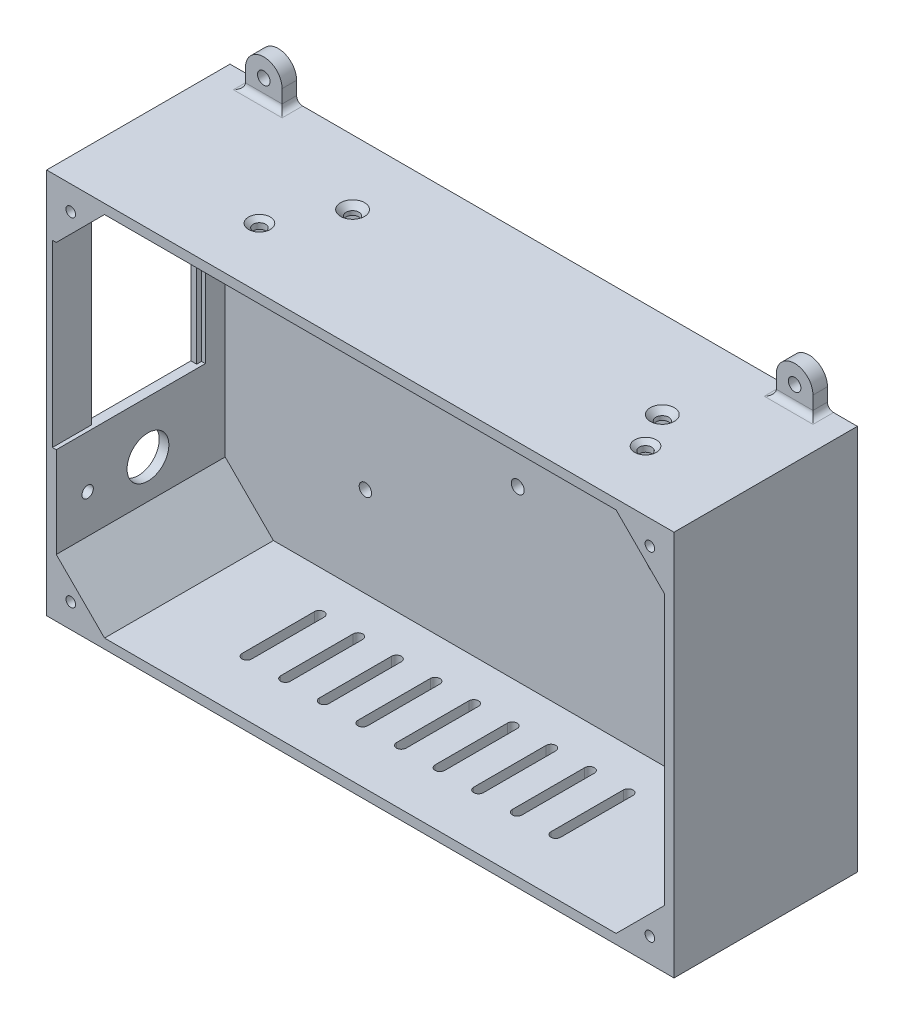
SolidWorks part; units mm, degrees
material "PET"
ref_plane "Front Plane" through (0, 0, 0) normal (0, 0, 1) x (1, 0, 0)
ref_plane "Top Plane" through (0, 0, 0) normal (0, 1, 0) x (1, 0, 0)
ref_plane "Right Plane" through (0, 0, 0) normal (1, 0, 0) x (0, 0, -1)
sketch "Sketch1" plane through (0, 0, 0) normal (0, 0, 1) x (1, 0, 0)
  line L1 (0, 0) -> (165.1, 0)
  line L2 (0, 0) -> (0, 101.6)
  line L3 (0, 101.6) -> (165.1, 101.6)
  line L4 (165.1, 0) -> (165.1, 101.6)
  dimension "D1" = 101.6
  dimension "D2" = 165.1
extrude "Boss-Extrude1" add sketch "Sketch1" along normal blind 3.81
sketch "Sketch2" plane through (0, 0, 3.81) normal (0, 0, 1) x (1, 0, 0)
  line L0 (165.1, 101.6) -> (0, 101.6)
  line L1 (0, 101.6) -> (0, 0)
  line L2 (0, 0) -> (165.1, 0)
  line L3 (165.1, 0) -> (165.1, 101.6)
  line L4 (2.54, 99.06) -> (162.56, 99.06)
  line L5 (162.56, 99.06) -> (162.56, 2.54)
  line L6 (162.56, 2.54) -> (2.54, 2.54)
  line L7 (2.54, 2.54) -> (2.54, 99.06)
  dimension "D1" = 2.54
  dimension "D2" = 2.54
  dimension "D3" = 2.54
  dimension "D4" = 2.54
extrude "Boss-Extrude2" add sketch "Sketch2" along normal blind 44.45
sketch "Sketch3" plane through (0, 0, 3.81) normal (0, 0, 1) x (1, 0, 0)
  line L0 (165.1, 0) -> (165.1, 101.6) construction
  line L1 (165.1, 101.6) -> (0, 101.6) construction
  line L2 (149.86, 99.06) -> (162.56, 86.36)
  line L3 (162.56, 99.06) -> (2.54, 99.06) construction
  line L4 (162.56, 2.54) -> (162.56, 99.06) construction
  line L5 (162.56, 86.36) -> (162.56, 99.06)
  line L6 (162.56, 99.06) -> (149.86, 99.06)
  circle A0 centre (158.75, 95.25) radius 3.81 construction
  circle A1 centre (158.75, 95.25) radius 1.27
  dimension "D1" = 7.62
  dimension "D4" = 2.54
  dimension "D2" = 6.35
  dimension "D3" = 6.35
  dimension "D5" = 12.7
extrude "Boss-Extrude3" add sketch "Sketch3" along normal up to surface (44.45 mm away) contours L2 L5 L6 up to face at (82.55, 50.8, 48.26)
extrude "Cut-Extrude1" cut sketch "Sketch3<3>" against normal blind 15.875 from surface contours A1 starting at face at (82.55, 50.8, 48.26)
sketch "Sketch3<3>" plane through (0, 0, 3.81) normal (0, 0, 1) x (1, 0, 0) same geometry as "Sketch3"
ref_plane "Plane1" through (82.55, 0, 0) normal (1, 0, 0) x (0, 0, -1)
mirror "Mirror1" about plane through (82.55, 0, 0) normal (1, 0, 0) of "Cut-Extrude1", "Boss-Extrude3"
ref_plane "Plane2" through (0, 50.8, 0) normal (0, -1, 0) x (-1, 0, 0)
mirror "Mirror2" about plane through (0, 50.8, 0) normal (0, -1, 0) of "Mirror1"
sketch "Sketch6" plane through (0, 0, 0) normal (-1, 0, 0) x (0, 0, 1)
  line L0 (24.13, 0) -> (24.13, 25.4) construction
  line L1 (48.26, 0) -> (0, 0) construction
  line L2 (24.13, 86.36) -> (24.13, 101.6) construction
  line L3 (10.287, 86.36) -> (37.973, 86.36)
  line L4 (10.287, 86.36) -> (10.287, 39.116)
  line L5 (10.287, 39.116) -> (37.973, 39.116)
  line L6 (37.973, 86.36) -> (37.973, 39.116)
  line L7 (48.26, 101.6) -> (0, 101.6) construction
  circle A0 centre (24.13, 25.4) radius 5.5
  dimension "D1" = 11
  dimension "D2" = 25.4
  dimension "D3" = 27.686
  dimension "D4" = 47.244
  dimension "D5" = 15.24
extrude "Cut-Extrude2" cut sketch "Sketch6" against normal up to next
sketch "Sketch7" plane through (0, 0, 48.26) normal (0, 0, 1) x (1, 0, 0)
  line L0 (2.54, 86.36) -> (2.54, 15.24) construction
  line L1 (2.54, 86.36) -> (1.524, 86.36)
  line L2 (2.54, 86.36) -> (2.54, 39.116)
  line L3 (2.54, 39.116) -> (1.524, 39.116)
  line L4 (1.524, 86.36) -> (1.524, 39.116)
  line L5 (0, 101.6) -> (0, 0) construction
  dimension "D1" = 1.524
extrude "Cut-Extrude3" cut sketch "Sketch7" against normal offset from surface (39.243 mm away) 1.27 up to face at (1.27, 62.738, 10.287) offset beyond the face yes
sketch "Sketch8" plane through (0, 0, 0) normal (0, 0, -1) x (-1, 0, 0)
  line L0 (-165.1, 0) -> (-165.1, 101.6) construction
  line L1 (-165.1, 101.6) -> (0, 101.6) construction
  line L2 (-157.226, 106.68) -> (-157.226, 101.6)
  line L3 (-157.226, 101.6) -> (-147.574, 101.6)
  line L4 (-147.574, 101.6) -> (-147.574, 106.68)
  line L5 (-165.1, 50.8) -> (0, 50.8) construction
  line L6 (0, 101.6) -> (0, 0) construction
  line L7 (-147.574, 0) -> (-147.574, -5.08)
  line L8 (-157.226, 0) -> (-147.574, 0)
  line L9 (-157.226, -5.08) -> (-157.226, 0)
  circle A0 centre (-152.4, 106.68) radius 1.651
  arc A1 (-147.574, 106.68) -> (-157.226, 106.68) centre (-152.4, 106.68) ccw
  arc A2 (-147.574, -5.08) -> (-157.226, -5.08) centre (-152.4, -5.08) cw
  circle A3 centre (-152.4, -5.08) radius 1.651
  dimension "D1" = 3.302
  dimension "D2" = 3.175
  dimension "D3" = 12.7
  dimension "D4" = 5.08
extrude "Boss-Extrude4" add sketch "Sketch8" against normal blind 3.81
fillet "Fillet1" radius 1.5875 6 edges at (157.226, 101.6, 1.905) (147.574, 101.6, 1.905) (152.4, 101.6, 3.81) (147.574, 0, 1.905) (152.4, 0, 3.81) (157.226, 0, 1.905)
mirror "Mirror5" about plane through (82.55, 0, 0) normal (1, 0, 0) of "Fillet1", "Boss-Extrude4"
sketch "Sketch9" plane through (0, 0, 0) normal (0, -1, 0) x (1, 0, 0)
  line L0 (38.1, 33.655) -> (38.1, 14.605) construction
  line L1 (39.37, 33.655) -> (39.37, 14.605)
  line L2 (36.83, 33.655) -> (36.83, 14.605)
  line L3 (38.1, 24.13) -> (0, 24.13) construction
  line L4 (0, 48.26) -> (0, 0) construction
  arc A0 (39.37, 33.655) -> (36.83, 33.655) centre (38.1, 33.655) ccw
  arc A1 (36.83, 14.605) -> (39.37, 14.605) centre (38.1, 14.605) ccw
  point P2 (38.1, 24.13)
  dimension "D1" = 2.54
  dimension "D2" = 19.05
  dimension "D3" = 38.1
extrude "Cut-Extrude4" cut sketch "Sketch9" against normal up to next
pattern_linear "LPattern1" count 9 spacing 10.16 along (1, 0, 0) of "Cut-Extrude4"
sketch "Sketch10" plane through (0, 101.6, 0) normal (0, 1, 0) x (1, 0, 0)
  point P0 (141.7447, -32.3977)
  point P1 (136.7536, -22.987)
  point P3 (49.276, -17.018)
  point P5 (40.1447, -32.3977)
sketch "Sketch11" plane through (0, 0, 0) normal (0, 0, -1) x (-1, 0, 0)
  point P0 (-115.3414, 46.9392)
  point P1 (-79.5274, 46.9392)
  point P3 (-79.5274, 74.6252)
  point P5 (-39.4335, 26.2255)
  point P7 (-141.8971, 93.3323)
hole_wizard "CSK for M3 Flat Head Machine Screw1" positions "Sketch12" profile "Sketch13" countersink size "M3" standard "ANSI Metric"
sketch "Sketch12" plane through (0, 0, 0) normal (0, 0, -1) x (-1, 0, 0)
  point P0 (-79.5274, 74.6252)
  point P3 (-79.5274, 46.9392)
  point P6 (-115.3414, 46.9392)
sketch "Sketch13" plane through (79.5274, 74.6252, 0) normal (1, 0, 0) x (0, 1, 0)
  line L0 (0, 0) -> (0, 7.3715)
  line L1 (0, 7.3715) -> (1.7, 6.35)
  line L2 (1.7, 6.35) -> (1.7, 1.45)
  line L3 (1.7, 1.45) -> (3.15, 0)
  line L5 (3.15, 0) -> (0, 0)
  line L6 (-1.7, 1.45) -> (-3.15, 0) construction
  line L10 (0, 7.3715) -> (-1.7, 6.35) construction
  line L11 (0, -6.35) -> (0, 107.95) construction
  dimension "Hole Dia." = 3.4
  dimension "Hole Depth" = 6.35
  dimension "Near C'Sink Dia." = 6.3
  dimension "Near C'Sink Angle" = 90
  dimension "Drill Angle" = 118
hole_wizard "CSK for M3 Flat Head Machine Screw2" positions "Sketch14" profile "Sketch15" countersink size "M3" standard "ANSI Metric"
sketch "Sketch14" plane through (0, 101.6, 0) normal (0, 1, 0) x (1, 0, 0)
  point P0 (49.276, -17.018)
  point P3 (136.7536, -22.987)
sketch "Sketch15" plane through (49.276, 101.6, 17.018) normal (1, 0, 0) x (0, 0, 1)
  line L0 (0, 0) -> (0, 7.3715)
  line L1 (0, 7.3715) -> (1.7, 6.35)
  line L2 (1.7, 6.35) -> (1.7, 1.45)
  line L3 (1.7, 1.45) -> (3.15, 0)
  line L5 (3.15, 0) -> (0, 0)
  line L6 (-1.7, 1.45) -> (-3.15, 0) construction
  line L10 (0, 7.3715) -> (-1.7, 6.35) construction
  line L11 (0, -6.35) -> (0, 107.95) construction
  dimension "Hole Dia." = 3.4
  dimension "Hole Depth" = 6.35
  dimension "Near C'Sink Dia." = 6.3
  dimension "Near C'Sink Angle" = 90
  dimension "Drill Angle" = 118
hole_wizard "CSK for #4 Flat Head Machine Screw (100)1" positions "Sketch16" profile "Sketch17" countersink size "#4" standard "ANSI Inch"
sketch "Sketch16" plane through (0, 101.6, 0) normal (0, 1, 0) x (1, 0, 0)
  point P0 (40.1447, -32.3977)
  point P3 (141.7447, -32.3977)
sketch "Sketch17" plane through (40.1447, 101.6, 32.3977) normal (1, 0, 0) x (0, 0, 1)
  line L0 (0, 0) -> (0, 7.3306)
  line L1 (0, 7.3306) -> (1.6319, 6.35)
  line L2 (1.6319, 6.35) -> (1.6319, 1.0284)
  line L3 (1.6319, 1.0284) -> (2.8575, 0)
  line L5 (2.8575, 0) -> (0, 0)
  line L6 (-1.6319, 1.0284) -> (-2.8575, 0) construction
  line L10 (0, 7.3306) -> (-1.632, 6.35) construction
  line L11 (0, -6.35) -> (0, 107.95) construction
  dimension "Hole Dia." = 3.2639
  dimension "Hole Depth" = 6.35
  dimension "Near C'Sink Dia." = 5.715
  dimension "Near C'Sink Angle" = 100
  dimension "Drill Angle" = 118
hole_wizard "CSK for #4 Flat Head Machine Screw (100)2" positions "Sketch18" profile "Sketch19" countersink size "#4" standard "ANSI Inch"
sketch "Sketch18" plane through (0, 0, 0) normal (0, 0, -1) x (-1, 0, 0)
  point P0 (-39.4335, 26.2255)
  point P3 (-141.8971, 93.3323)
sketch "Sketch19" plane through (39.4335, 26.2255, 0) normal (1, 0, 0) x (0, 1, 0)
  line L0 (0, 0) -> (0, 7.3306)
  line L1 (0, 7.3306) -> (1.6319, 6.35)
  line L2 (1.6319, 6.35) -> (1.6319, 1.0284)
  line L3 (1.6319, 1.0284) -> (2.8575, 0)
  line L5 (2.8575, 0) -> (0, 0)
  line L6 (-1.6319, 1.0284) -> (-2.8575, 0) construction
  line L10 (0, 7.3306) -> (-1.6319, 6.35) construction
  line L11 (0, -6.35) -> (0, 107.95) construction
  dimension "Hole Dia." = 3.2639
  dimension "Hole Depth" = 6.35
  dimension "Near C'Sink Dia." = 5.715
  dimension "Near C'Sink Angle" = 100
  dimension "Drill Angle" = 118
sketch "Sketch20" plane through (2.54, 0, 0) normal (1, 0, 0) x (0, 0, -1)
  line L0 (-24.13, 25.4) -> (-40.005, 25.4) construction
  circle A0 centre (-40.005, 25.4) radius 1.5
  dimension "D1" = 3
  dimension "D2" = 15.875
extrude "Cut-Extrude5" cut sketch "Sketch20" against normal up to next
